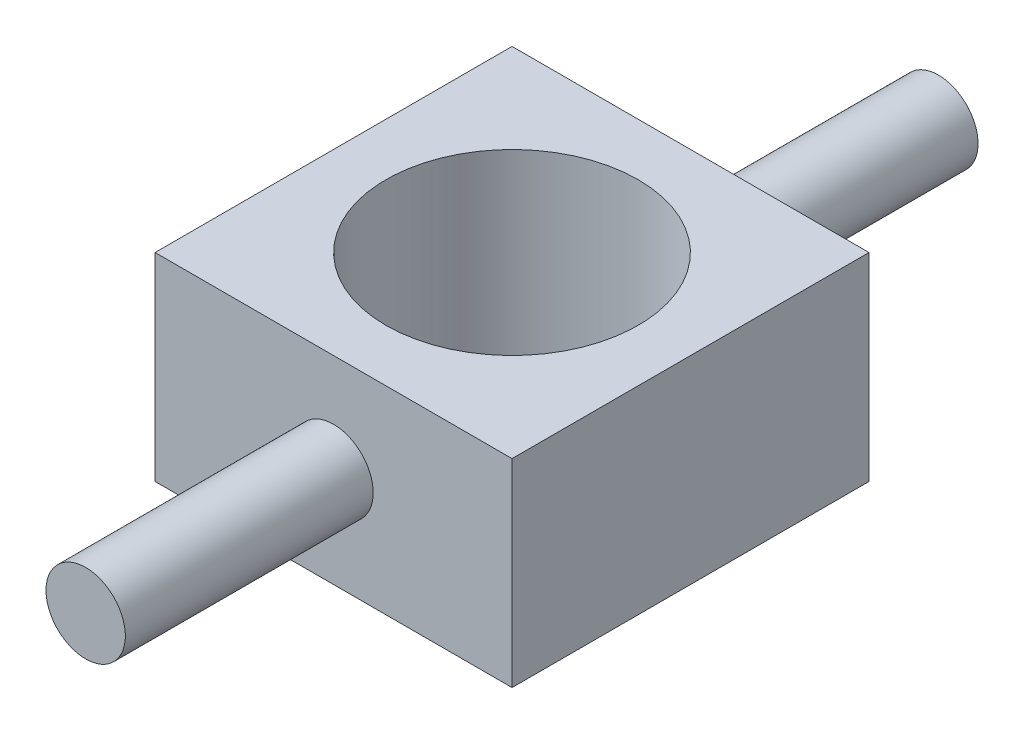
SolidWorks part; units mm, degrees
ref_plane "Front Plane" through (0, 0, 0) normal (0, 0, 1) x (1, 0, 0)
ref_plane "Top Plane" through (0, 0, 0) normal (0, 1, 0) x (1, 0, 0)
ref_plane "Right Plane" through (0, 0, 0) normal (1, 0, 0) x (0, 0, -1)
sketch "Sketch1" plane through (0, 0, 0) normal (0, 1, 0) x (1, 0, 0)
  line L1 (-18, 18) -> (18, 18)
  line L2 (-18, 18) -> (-18, -18)
  line L3 (-18, -18) -> (18, -18)
  line L4 (18, 18) -> (18, -18)
  line L5 (-18, 18) -> (18, -18) construction
  line L6 (-18, -18) -> (18, 18) construction
  point P0 (0, 0)
  dimension "D1" = 36
  dimension "D2" = 36
extrude "Boss-Extrude1" add sketch "Sketch1" along normal blind 10 and the other way blind 10
sketch "Sketch2" plane through (0, -10, 0) normal (0, -1, 0) x (1, 0, 0)
  circle A0 centre (0, 0) radius 12.725
  dimension "D1" = 25.45
extrude "Cut-Extrude1" cut sketch "Sketch2" against normal through all
sketch "Sketch5" plane through (0, 0, -18) normal (0, 0, -1) x (-1, 0, 0)
  circle A0 centre (0, 0) radius 4
  dimension "D1" = 8
extrude "Boss-Extrude2" add sketch "Sketch5" along normal blind 25
mirror "Mirror1" about plane through (0, 0, 0) normal (0, 0, 1) of "Boss-Extrude2"
